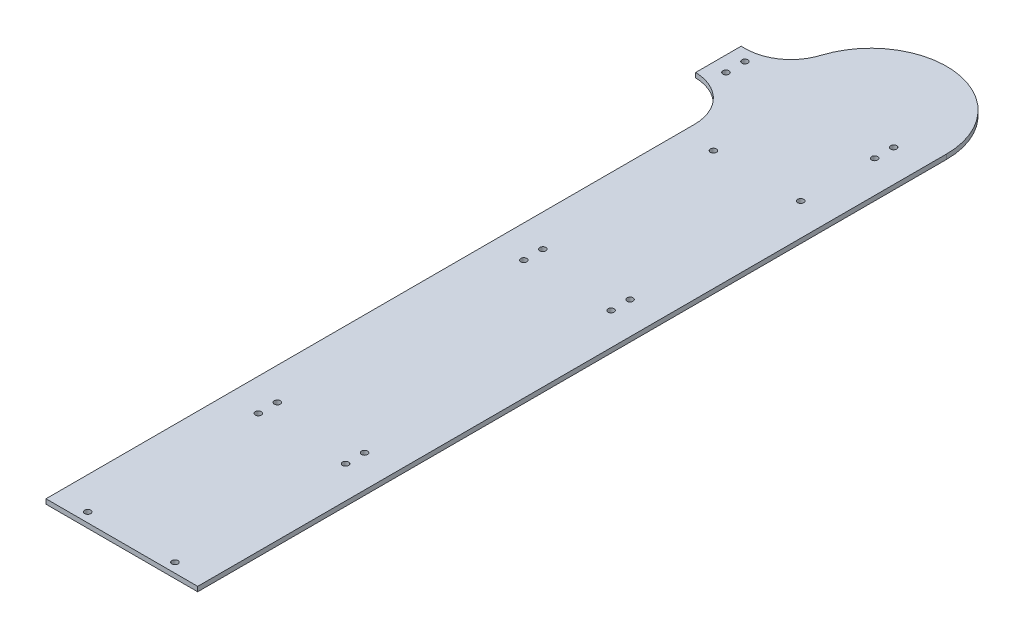
SolidWorks part; units mm, degrees
ref_plane "Front Plane" through (0, 0, 0) normal (0, 0, 1) x (1, 0, 0)
ref_plane "Top Plane" through (0, 0, 0) normal (0, 1, 0) x (1, 0, 0)
ref_plane "Right Plane" through (0, 0, 0) normal (1, 0, 0) x (0, 0, -1)
sketch "Sketch1" plane through (0, 0, 0) normal (0, 1, 0) x (1, 0, 0)
  line L2 (0, 0) -> (0, -495.3)
  line L3 (0, -495.3) -> (101.6, -495.3)
  line L4 (101.6, 0) -> (101.6, -495.3)
  arc A0 (0, 0) -> (101.6, 0) centre (50.8, -38.1) cw
  dimension "D3" = 63.5
  dimension "D1" = 495.3
  dimension "D2" = 101.6
extrude "Boss-Extrude1" add sketch "Sketch1" along normal blind 3.175
sketch "Sketch2" plane through (0, 0, 0) normal (0, -1, 0) x (1, 0, 0)
  line L0 (21.59, 69.85) -> (80.01, 69.85) construction
  line L1 (0, 495.3) -> (101.6, 495.3) construction
  circle A0 centre (21.59, 488.95) radius 2.032
  circle A1 centre (80.01, 488.95) radius 2.032
  circle A2 centre (21.59, 69.85) radius 2.032
  circle A3 centre (80.01, 69.85) radius 2.032
  arc A4 (0, 0) -> (101.6, 0) centre (50.8, 38.1) ccw construction
  circle A5 centre (21.59, 196.85) radius 2.032
  circle A6 centre (80.01, 196.85) radius 2.032
  circle A7 centre (21.59, 184.15) radius 2.032
  circle A8 centre (80.01, 184.15) radius 2.032
  circle A9 centre (21.59, 361.95) radius 2.032
  circle A10 centre (80.01, 361.95) radius 2.032
  circle A11 centre (21.59, 374.65) radius 2.032
  circle A12 centre (80.01, 374.65) radius 2.032
  point P11 (50.8, -25.4)
  point P12 (50.8, 69.85)
  dimension "D1" = 4.064
  dimension "D2" = 58.42
  dimension "D3" = 6.35
  dimension "D4" = 419.1
  dimension "D5" = 114.3
  dimension "D6" = 177.8
  dimension "D7" = 12.7
  dimension "D8" = 12.7
extrude "Cut-Extrude1" cut sketch "Sketch2" against normal through all
sketch "Sketch6" plane through (0, 3.175, 0) normal (0, 1, 0) x (1, 0, 0)
sketch "Sketch10" plane through (0, 0, 0) normal (0, -1, 0) x (-1, 0, 0)
  line L2 (0, 0) -> (76.2, 0)
  line L3 (0, 0) -> (0, -152.4)
  line L4 (0, -152.4) -> (76.2, -152.4)
  line L5 (76.2, 0) -> (76.2, -152.4)
  dimension "D1" = 152.4
  dimension "D2" = 76.2
extrude "Boss-Extrude6" add sketch "Sketch10" against normal up to surface (3.175 mm away) up to face at (80.01, 3.175, 194.818)
sketch "Sketch8" plane through (0, 0, 0) normal (0, -1, 0) x (-1, 0, 0)
  line L0 (-80.01, -67.818) -> (-80.01, -50.8583) construction
  line L1 (0, -495.3) -> (-101.6, -495.3) construction
  circle A0 centre (19.558, -20.3073) radius 2.032
  circle A1 centre (-80.01, -20.3073) radius 2.032
  circle A2 centre (19.558, -7.6073) radius 2.032
  circle A3 centre (-80.01, -7.6073) radius 2.032
  circle A4 centre (-80.01, -69.85) radius 2.032 construction
  dimension "D1" = 4.064
  dimension "D2" = 99.568
  dimension "D3" = 12.7
  dimension "D4" = 474.9927
extrude "Cut-Extrude4" cut sketch "Sketch8" against normal through all
sketch "Sketch16" plane through (0, 0, 0) normal (0, -1, 0) x (-1, 0, 0)
  line L0 (76.2, -152.4) -> (76.2, 0) construction
  line L1 (0, -152.4) -> (76.2, -152.4)
  line L2 (0, -152.4) -> (0, -30.4673)
  line L3 (0, -30.4673) -> (76.2, -30.4673)
  line L4 (76.2, -152.4) -> (76.2, -30.4673)
  line L6 (0, 0) -> (76.2, 0)
  line L7 (0, 0) -> (0, 2.5527)
  line L8 (0, 2.5527) -> (76.2, 2.5527)
  line L9 (76.2, 0) -> (76.2, 2.5527)
  line L10 (76.2, -30.4673) -> (29.718, -30.4673)
  line L11 (76.2, -30.4673) -> (76.2, 2.5527)
  line L12 (76.2, 2.5527) -> (29.718, 2.5527)
  line L13 (29.718, -30.4673) -> (29.718, 2.5527)
  circle A0 centre (19.558, -20.3073) radius 2.032 construction
  circle A1 centre (19.558, -7.6073) radius 2.032 construction
  line M27 (0, -152.4) -> (76.2, -152.4)
  line M28 (76.2, -152.4) -> (76.2, 0)
  line M29 (76.2, 0) -> (0, 0)
  dimension "D1" = 10.16
  dimension "D2" = 10.16
  dimension "D3" = 10.16
extrude "Cut-Extrude5" cut sketch "Sketch16" against normal through all contours L3 L2 M27 M28 | L13 L3 L8 M28 | L7 L8 M28 M29 region at (-38.1, 0, 91.4336) region at (-52.959, 0, 15.2336)
sketch "Sketch17" plane through (0, 0, 0) normal (0, -1, 0) x (1, 0, 0)
  line L0 (101.6, 495.3) -> (101.6, 0) construction
  line L1 (16.9061, 42.1497) -> (27.1204, 42.1497)
  line L2 (16.9061, 42.1497) -> (16.9061, 32.6649)
  line L3 (16.9061, 32.6649) -> (27.1204, 32.6649)
  line L4 (27.1204, 42.1497) -> (27.1204, 32.6649)
  line L5 (75.0662, 40.806) -> (85.3535, 40.806)
  line L6 (75.0662, 40.806) -> (75.0662, 35.2727)
  line L7 (75.0662, 35.2727) -> (85.3535, 35.2727)
  line L8 (85.3535, 40.806) -> (85.3535, 35.2727)
  line L9 (0, 10.1473) -> (-29.718, 10.1473) construction
  line L10 (0, 30.4673) -> (0, 495.3) construction
  dimension "D1" = 5.5333
  dimension "D2" = 10.2873
  dimension "D3" = 16.2465
  dimension "D4" = 25.1254
  dimension "D5" = 10.2143
  dimension "D6" = 9.4847
  dimension "D7" = 16.9061
  dimension "D8" = 22.5176
extrude "Boss-Extrude11" add sketch "Sketch17" against normal up to surface (3.175 mm away) up to face at (21.59, 3.175, 486.918)
fillet "Fillet1" radius 30.48 1 edges at (0, 1.5875, 30.4673)
sketch "Sketch20" plane through (0, 3.175, 0) normal (0, 1, 0) x (1, 0, 0)
  line L0 (0, 0) -> (0, 6.35)
  line L1 (101.6, 0) -> (101.6, 6.35)
  arc A1 (0, 6.35) -> (101.6, 6.35) centre (50.8, 6.35) cw
  arc A4 (101.6, 0) -> (0, 0) centre (50.8, -38.1) ccw
  arc A5 (101.6, 0) -> (0, 0) centre (50.8, -38.1) ccw
  dimension "D1" = 6.35
  dimension "D2" = 0
extrude "Boss-Extrude12" add sketch "Sketch20" against normal up to surface (3.175 mm away) up to face at (80.01, 0, 18.2753)
fillet "Fillet2" radius 30.48 1 edges at (0, 1.5875, 0)
